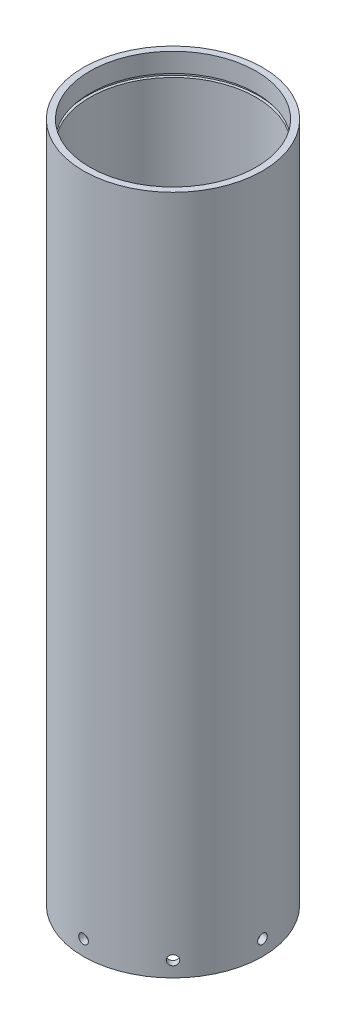
SolidWorks part; units mm, degrees
material "1060 Alloy"
ref_plane "Front Plane" through (0, 0, 0) normal (0, 0, 1) x (1, 0, 0)
ref_plane "Top Plane" through (0, 0, 0) normal (0, 1, 0) x (1, 0, 0)
ref_plane "Right Plane" through (0, 0, 0) normal (1, 0, 0) x (0, 0, -1)
sketch "Sketch2" plane through (0, 0, 0) normal (0, 0, 1) x (1, 0, 0)
  line L0 (0, 0) -> (0, 365.76) construction
  line L3 (41.275, 0) -> (44.45, 0)
  line L4 (41.275, 337.566) -> (41.275, 328.041)
  line L5 (41.275, 337.566) -> (44.45, 337.566)
  line L6 (44.45, 0) -> (44.45, 337.566)
  line L8 (41.275, 326.3138) -> (42.5958, 326.3138)
  line L9 (42.5958, 326.3138) -> (42.5958, 328.041)
  line L10 (42.5958, 328.041) -> (41.275, 328.041)
  line L11 (41.275, 326.3138) -> (41.275, 163.1569)
  line L12 (41.275, 163.1569) -> (41.2565, 163.1312)
  line L13 (41.275, 163.1569) -> (41.275, 0)
  line L14 (0, -55) -> (0, 55) construction
  point P2 (0, 0)
  dimension "D2" = 9.525
  dimension "D3" = 3.175
  dimension "D4" = 337.566
  dimension "D9" = 1.3208
  dimension "D10" = 1.7272
revolve "Revolve1" add sketch "Sketch2" angle 360 about L0 region at (42.8645, 168.4451, 0)
ref_axis "Axis1" through (0, -17.0472, 0) along (0, 1, 0)
ref_plane "Plane1" through (0, 7.62, 0) normal (0, -1, 0) x (-1, 0, 0)
ref_axis "Axis2" through (0, 7.62, 88.99) along (0, 0, -1)
hole_wizard "3/16 (0.1875) Diameter Hole1" positions "3DSketch1" profile "Sketch3" hole size "3/16" standard "ANSI Inch" end condition up to next
sketch3d "3DSketch1"
  line L0 (0, 7.62, 88.99) -> (0, 7.62, -88.99) construction
  point P0 (0, 7.62, -44.45)
  point P3 (0, 0, 0)
sketch "Sketch3" plane through (0, 7.62, -44.45) normal (1, 0, 0) x (0, 1, 0)
  line L0 (0, 0) -> (0, 3.175)
  line L1 (0, 3.175) -> (2.3812, 3.175)
  line L2 (2.3812, 3.175) -> (2.3812, 0)
  line L5 (2.3812, 0) -> (0, 0)
  line L11 (0, -6.35) -> (0, 107.95) construction
  dimension "Thru Hole Dia." = 4.7625
  dimension "Thru Hole Depth" = 3.175
pattern_circular "CirPattern1" count 8 over 360 about axis through (0, -17.0472, 0) along (0, 1, 0) of "3/16 (0.1875) Diameter Hole1"
